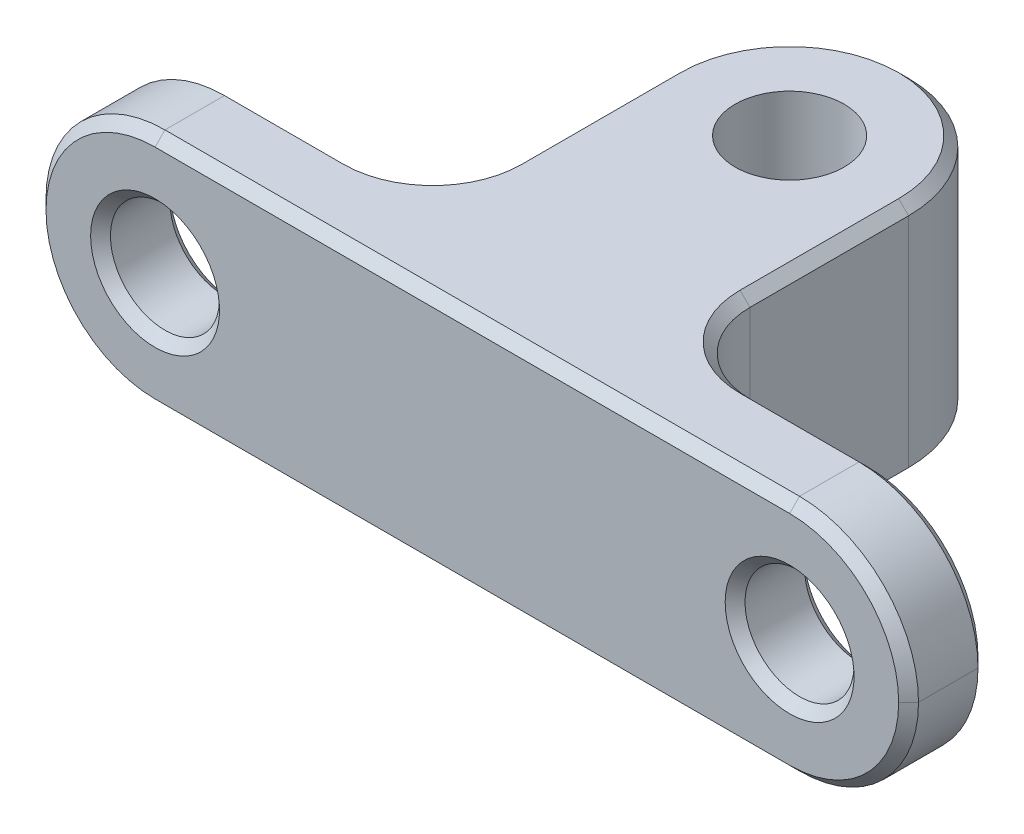
SolidWorks part; units mm, degrees
ref_plane "Front Plane" through (0, 0, 0) normal (0, 0, 1) x (1, 0, 0)
ref_plane "Top Plane" through (0, 0, 0) normal (0, 1, 0) x (1, 0, 0)
ref_plane "Right Plane" through (0, 0, 0) normal (1, 0, 0) x (0, 0, -1)
sketch "Sketch1" plane through (0, 0, 0) normal (0, 1, 0) x (1, 0, 0)
  line L0 (-4.7625, 0) -> (-4.7625, -9.525)
  line L1 (-4.7625, -9.525) -> (-17.4625, -9.525)
  line L2 (-17.4625, -9.525) -> (-17.4625, -12.7)
  line L3 (-17.4625, -12.7) -> (17.4625, -12.7)
  line L4 (17.4625, -12.7) -> (17.4625, -9.525)
  line L5 (17.4625, -9.525) -> (4.7625, -9.525)
  line L6 (4.7625, -9.525) -> (4.7625, 0)
  arc A0 (4.7625, 0) -> (-4.7625, 0) centre (0, 0) ccw
  circle A1 centre (0, 0) radius 2.1828
  dimension "D1" = 4.7625
  dimension "D2" = 4.3656
  dimension "D3" = 12.7
  dimension "D4" = 3.175
  dimension "D5" = 12.7
  dimension "D6" = 12.7
extrude "Boss-Extrude1" add sketch "Sketch1" along normal blind 9.525
sketch "Sketch2" plane through (0, 0, 9.525) normal (0, 0, -1) x (-1, 0, 0)
  circle A0 centre (-12.7, 4.7625) radius 2.1828
  circle A1 centre (12.7, 4.7625) radius 2.1828
  point P4 (0, 0)
  dimension "D4" = 4.3656
  dimension "D5" = 4.3656
  dimension "D1" = 12.7
  dimension "D2" = 12.7
  dimension "D3" = 4.7625
extrude "Cut-Extrude1" cut sketch "Sketch2" against normal through all both and the other way through all
fillet "Fillet1" radius 4.7625 4 edges at (17.4625, 9.525, 11.1125) (17.4625, 0, 11.1125) (-17.4625, 9.525, 11.1125) (-17.4625, 0, 11.1125)
fillet "Fillet2" radius 3.175 2 edges at (4.7625, 4.7625, 9.525) (-4.7625, 4.7625, 9.525)
chamfer "Chamfer1" distance 0.3969 angle 45 29 edges at (14.8828, 4.7625, 9.525) (10.5172, 4.7625, 12.7) (-10.5172, 4.7625, 9.525) (-14.8828, 4.7625, 12.7) (0, 0, 2.1828) (0, 9.525, 12.7) (-16.0676, 8.1301, 12.7) (16.0676, 8.1301, 12.7) (-16.0676, 1.3949, 12.7) (16.0676, 1.3949, 12.7) (0, 0, 12.7) (0, 9.525, -4.7625) (-4.7625, 9.525, 3.175) (4.7625, 9.525, 3.175) (-5.6924, 9.525, 8.5951) (5.6924, 9.525, 8.5951) (-10.3187, 9.525, 9.525) (10.3187, 9.525, 9.525) (-16.0676, 8.1301, 9.525) (16.0676, 8.1301, 9.525) (-16.0676, 1.3949, 9.525) (16.0676, 1.3949, 9.525) (-10.3187, 0, 9.525) (-5.6924, 0, 8.5951) (-4.7625, 0, 3.175) (0, 0, -4.7625) (4.7625, 0, 3.175) (5.6924, 0, 8.5951) (10.3187, 0, 9.525)
